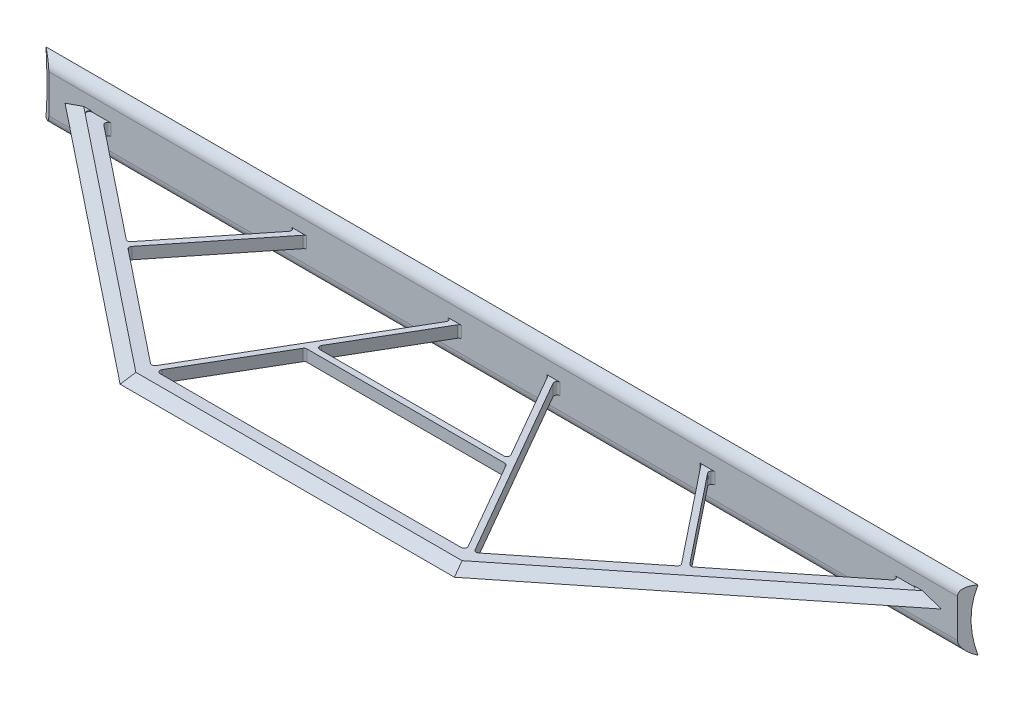
SolidWorks part; units mm, degrees
material "6061-T6 (SS)"
ref_plane "Front Plane" through (0, 0, 0) normal (0, 0, 1) x (1, 0, 0)
ref_plane "Top Plane" through (0, 0, 0) normal (0, 1, 0) x (1, 0, 0)
ref_plane "Right Plane" through (0, 0, 0) normal (1, 0, 0) x (0, 0, -1)
sketch "CS path" plane through (0, 0, 0) normal (0, 1, 0) x (1, 0, 0)
  line L0 (0, 0) -> (-228.6, 0) construction
  line L1 (0, 0) -> (228.6, 0) construction
  line L2 (0, 0) -> (0, -111.2988) construction
  line L3 (0, -111.2988) -> (88.9, -111.2988) construction
  line L4 (0, -111.2988) -> (-88.9, -111.2988) construction
  line L5 (88.9, -111.2988) -> (228.6, 0) construction
  line L6 (-88.9, -111.2988) -> (88.9, -111.2988)
  line L8 (228.6, 0) -> (248.466, 15.8272) construction
  line L9 (-88.9, -111.2988) -> (-228.6, 0) construction
  line L10 (-228.6, 0) -> (-248.466, 15.8272) construction
  line L11 (88.9, -111.2988) -> (248.466, 15.8272)
  line L12 (-88.9, -111.2988) -> (-248.466, 15.8272)
ref_plane "Plane4" through (248.466, 0, -15.8272) normal (0.7821, 0, -0.6231) x (-0.6231, 0, -0.7821)
sketch "Sketch7" plane through (248.466, 0, -15.8272) normal (0.7821, 0, -0.6231) x (-0.6231, 0, -0.7821)
  line L0 (0, 0) -> (0, 3.175) construction
  line L1 (110.7906, 0) -> (0, 0) construction
  line L2 (0, 3.175) -> (6.35, 3.175) construction
  line L3 (0, 0) -> (-6.35, 0) construction
  line L4 (0, 3.175) -> (0, 3.556)
  line L5 (6.35, 3.175) -> (0, 3.175)
  line L6 (0, 3.556) -> (-6.35, 0)
  line L7 (6.35, 3.175) -> (6.35, -3.175)
  line L8 (6.35, -3.175) -> (0, -3.175)
  line L9 (0, -3.175) -> (0, -3.556)
  line L10 (0, -3.556) -> (-6.35, 0)
sweep "Sweep2" add profiles "Sketch7" path "CS path"
sketch "Sketch8" plane through (0, 0, 0) normal (1, 0, 0) x (0, 0, -1)
  line L0 (0, 0) -> (82.804, 0) construction
  line L1 (82.804, 0) -> (-43.02, 26.7447) construction
  line L2 (82.804, 0) -> (-44.9942, -27.1644) construction
  line L3 (4.8299, 16.5739) -> (0, 17.6005)
  line L4 (4.8299, -16.5739) -> (0, -17.6005)
  line L5 (0, 17.6005) -> (0, -17.6005)
  line L6 (3.175, 0) -> (86.995, 0) construction
  arc A0 (4.8299, 16.5739) -> (4.8299, -16.5739) centre (86.995, 0) ccw
  dimension "D1" = 12
  dimension "D2" = 12
extrude "Boss-Extrude3" add sketch "Sketch8" along normal blind 254 and the other way blind 254 separate body
sketch "Sketch11" plane through (0, 0, 0) normal (0, 1, 0) x (1, 0, 0)
  line L3 (-86.6797, -104.9488) -> (-25.4, 0) construction
  line L4 (25.4, 0) -> (86.6797, -104.9488) construction
  line L6 (-25.4, 0) -> (-15.0913, 17.6549) construction
  line L7 (-86.6797, -104.9488) -> (-89.1388, -109.1603) construction
  line L8 (-89.1388, -109.1603) -> (-15.0913, 17.6549)
ref_plane "Plane5" through (-15.0913, 0, -17.6549) normal (0.5042, 0, -0.8636) x (-0.8636, 0, -0.5042)
sketch "Sketch12" plane through (-15.0913, 0, -17.6549) normal (0.5042, 0, -0.8636) x (-0.8636, 0, -0.5042)
  line L0 (0, 0) -> (0, -3.175) construction
  line L1 (0, -3.175) -> (1.5875, -3.175) construction
  line L2 (1.5875, -3.175) -> (1.5875, 3.175) construction
  line L3 (0, -3.175) -> (1.5875, -3.175)
  line L4 (1.5875, -3.175) -> (1.5875, 3.175)
  line L5 (1.5875, 3.175) -> (-1.5875, 3.175)
  line L6 (-1.5875, 3.175) -> (-1.5875, -3.175)
  line L7 (-1.5875, -3.175) -> (0, -3.175)
sweep "Sweep3" add profiles "Sketch12" path "Sketch11"
sketch "Sketch13" plane through (0, 0, 0) normal (0, 1, 0) x (1, 0, 0)
  line L2 (25.3355, 1.8095) -> (86.6797, -104.9488) construction
  line L3 (86.6797, -104.9488) -> (89.8434, -110.4546) construction
  line L4 (89.8434, -110.4546) -> (12.6343, 23.9135)
  line L5 (25.3355, 1.8095) -> (12.6343, 23.9135) construction
ref_plane "Plane6" through (12.6343, 0, -23.9135) normal (-0.4982, 0, -0.8671) x (-0.8671, 0, 0.4982)
sketch "Sketch14" plane through (12.6343, 0, -23.9135) normal (-0.4982, 0, -0.8671) x (-0.8671, 0, 0.4982)
  line L0 (0, 0) -> (0, -3.175) construction
  line L1 (0, -3.175) -> (1.5875, -3.175) construction
  line L2 (1.5875, -3.175) -> (1.5875, 3.175) construction
  line L3 (1.5875, 3.175) -> (-1.5875, 3.175) construction
  line L4 (0, -3.175) -> (1.5875, -3.175)
  line L5 (1.5875, -3.175) -> (1.5875, 3.175)
  line L6 (1.5875, 3.175) -> (-1.5875, 3.175)
  line L7 (-1.5875, 3.175) -> (-1.5875, -3.175)
  line L8 (-1.5875, -3.175) -> (0, -3.175)
sweep "Sweep5" add profiles "Sketch14" path "Sketch13"
sketch "Sketch15" plane through (254, 0, 0) normal (1, 0, 0) x (0, 0, -1)
  line L0 (4.8299, -16.5739) -> (30.9499, -16.5739)
  line L1 (30.9499, 16.5739) -> (30.9499, -16.5739)
  line L2 (4.8299, 16.5739) -> (30.9499, 16.5739)
  arc A0 (4.8299, 16.5739) -> (4.8299, -16.5739) centre (86.995, 0) ccw construction
  arc A2 (4.8299, 16.5739) -> (4.8299, -16.5739) centre (86.995, 0) ccw
extrude "Cut-Extrude1" cut sketch "Sketch15" against normal blind 508
ref_plane "Plane7" through (0, 17.6005, 0) normal (0, -1, 0) x (1, 0, 0)
sketch "Sketch17" plane through (0, 17.6005, 0) normal (0, -1, 0) x (1, 0, 0)
  line L0 (254, 0) -> (247.65, 0)
  line L1 (254, -4.8299) -> (254, 0) construction
  line L2 (-254, 0) -> (254, 0) construction
  line L3 (254, -4.8299) -> (254, 0)
  line L4 (247.65, 0) -> (254, -4.8299)
extrude "Cut-Extrude2" cut sketch "Sketch17" along normal blind 68.58
sketch "Sketch18" plane through (0, 17.6005, 0) normal (0, -1, 0) x (1, 0, 0)
  line L0 (-254, -4.8299) -> (-254, 0) construction
  line L1 (-254, 0) -> (-247.65, 0)
  line L2 (-254, 0) -> (247.65, 0) construction
  line L3 (-247.65, 0) -> (-254, -4.8299)
  line L4 (-254, -4.8299) -> (-254, 0)
extrude "Cut-Extrude3" cut sketch "Sketch18" along normal blind 68.834
sketch "Sketch19" plane through (0, 3.175, 0) normal (0, 1, 0) x (1, 0, 0)
  line L0 (218.4093, 0) -> (228.6, 0) construction
  line L1 (88.9, -111.2988) -> (228.6, 0) construction
  line L2 (223.8781, 0) -> (228.6, 0)
  line L3 (224.9069, -2.9423) -> (228.6, 0)
  arc A0 (224.9069, -2.9423) -> (223.8781, 0) centre (223.8781, -1.651) ccw
  dimension "D1" = 3.302
extrude "Boss-Extrude4" add sketch "Sketch19" against normal blind 6.731 and the other way blind 0.381
sketch "Sketch20" plane through (0, -3.175, 0) normal (0, -1, 0) x (1, 0, 0)
  line L0 (-88.9, 111.2988) -> (-248.466, -15.8272) construction
  line L1 (-228.6, 0) -> (-218.4093, 0) construction
  line L2 (-224.9069, 2.9423) -> (-228.6, 0)
  line L3 (-228.6, 0) -> (-223.8781, 0)
  arc A0 (-224.9069, 2.9423) -> (-223.8781, 0) centre (-223.8781, 1.651) ccw
  dimension "D1" = 3.302
extrude "Boss-Extrude5" add sketch "Sketch20" along normal blind 0.381 and the other way blind 6.731
sketch "Sketch21" plane through (0, 3.175, 0) normal (0, 1, 0) x (1, 0, 0)
  line L0 (-87.9344, -103.9493) -> (-27.2383, 0) construction
  line L1 (-84.8414, -104.9488) -> (-23.5617, 0) construction
  line L2 (84.8488, -104.9488) -> (-84.8414, -104.9488) construction
  line L3 (-87.9344, -103.9493) -> (-218.4093, 0) construction
  line L4 (-87.9344, -103.9493) -> (-86.9722, -102.3015)
  line L5 (-84.8414, -104.9488) -> (-83.3913, -102.4653)
  line L6 (84.8488, -104.9488) -> (81.996, -104.9488)
  line L7 (-87.9344, -103.9493) -> (-89.4268, -102.7603)
  line L8 (-247.65, 0) -> (247.65, 0) construction
  line L9 (84.8488, -104.9488) -> (24.5443, 0) construction
  line L10 (87.9357, -103.9482) -> (28.2061, 0) construction
  line L11 (-218.4093, 0) -> (-213.6875, 0)
  line L12 (84.8488, -104.9488) -> (83.4275, -102.4753)
  line L13 (87.9357, -103.9482) -> (86.9783, -102.2821)
  line L14 (87.9357, -103.9482) -> (218.4093, 0) construction
  line L15 (87.9357, -103.9482) -> (89.4386, -102.7509)
  line L16 (-218.4093, 0) -> (31.0589, 0)
  line L17 (213.6875, 0) -> (218.4093, 0)
  line L18 (213.6875, 0) -> (218.4093, 0)
  line L19 (25.0203, -0.8284) -> (24.5443, 0)
  line L20 (29.6274, -2.4736) -> (28.2061, 0)
  line L21 (214.7162, -2.9423) -> (218.4093, 0)
  line L22 (-81.9656, -104.9488) -> (-84.8414, -104.9488)
  line L23 (23.5888, 0) -> (31.0589, 0)
  line L24 (-24.0396, -0.8185) -> (-23.5617, 0)
  line L25 (-28.6884, -2.4835) -> (-27.2383, 0)
  line L26 (-30.1142, 0) -> (-22.6139, 0)
  line L27 (-214.7162, -2.9423) -> (-218.4093, 0)
  arc A0 (-213.6875, 0) -> (-214.7162, -2.9423) centre (-213.6875, -1.651) ccw
  arc A1 (-89.4268, -102.7603) -> (-86.9722, -102.3015) centre (-88.398, -101.469) ccw
  arc A2 (-28.6884, -2.4835) -> (-30.1142, 0) centre (-30.1142, -1.651) ccw
  arc A3 (-22.6139, 0) -> (-24.0396, -0.8185) centre (-22.6139, -1.651) ccw
  arc A4 (25.0203, -0.8284) -> (23.5888, 0) centre (23.5888, -1.651) ccw
  arc A5 (81.996, -104.9488) -> (83.4275, -102.4753) centre (81.996, -103.2978) ccw
  arc A6 (-83.3913, -102.4653) -> (-81.9656, -104.9488) centre (-81.9656, -103.2978) ccw
  arc A7 (31.0589, 0) -> (29.6274, -2.4736) centre (31.0589, -1.651) ccw
  arc A8 (214.7162, -2.9423) -> (213.6875, 0) centre (213.6875, -1.651) ccw
  arc A9 (86.9783, -102.2821) -> (89.4386, -102.7509) centre (88.4098, -101.4596) ccw
  line M17 (218.4093, 0) -> (87.9357, -103.9482)
  line M18 (87.9357, -103.9482) -> (28.2061, 0)
  line M20 (24.5443, 0) -> (84.8488, -104.9488)
  line M21 (84.8488, -104.9488) -> (-84.8414, -104.9488)
  line M22 (-84.8414, -104.9488) -> (-23.5617, 0)
  line M24 (-27.2383, 0) -> (-87.9344, -103.9493)
  line M25 (-87.9344, -103.9493) -> (-218.4093, 0)
  dimension "D1" = 3.302
  dimension "D2" = 3.302
  dimension "D3" = 3.302
  dimension "D4" = 3.302
  dimension "D5" = 3.302
  dimension "D6" = 3.302
  dimension "D7" = 3.302
  dimension "D8" = 3.302
  dimension "D9" = 3.302
  dimension "D10" = 3.302
extrude "Boss-Extrude6" add sketch "Sketch21" against normal blind 6.35 contours A1 M25 M24 | A6 M22 M21 | A0 L11 M25 | A2 L16 M24 | A3 L16 M22 | A7 L16 M18 | A4 L16 M20 | A5 M21 M20 | A8 L17 M17 | A9 L15 L13 region at (-88.0555, 3.175, 103.3013) region at (216.155, 3.175, 0.7882) region at (29.2535, 3.175, 0.6061) region at (-23.4631, 3.175, 0.1717) region at (-28.2999, 3.175, 0.6095) region at (-216.155, 3.175, 0.7882) region at (24.4437, 3.175, 0.1739) region at (-83.7798, 3.175, 104.3394) region at (83.8014, 3.175, 104.3427)
sketch "Sketch22" plane through (0, 3.175, 0) normal (0, 1, 0) x (1, 0, 0)
  line L1 (-152.0715, -52.8513) -> (-214.7162, -2.9423) construction
  line L2 (-152.0715, -52.8513) -> (-108.201, 2.2141) construction
  line L3 (-152.0715, -52.8513) -> (-108.201, 2.2141)
ref_plane "Plane8" through (-152.0715, 3.175, 52.8513) normal (0.6231, 0, -0.7821) x (-0.7821, 0, -0.6231)
sketch "Sketch23" plane through (-152.0715, 3.175, 52.8513) normal (0.6231, 0, -0.7821) x (-0.7821, 0, -0.6231)
  line L0 (0, 0) -> (0, -6.35) construction
  line L2 (0, 0) -> (80.0954, 0) construction
  line L3 (0, -6.35) -> (1.5875, -6.35) construction
  line L4 (1.5875, -6.35) -> (1.5875, 0) construction
  line L5 (0, -6.35) -> (1.5875, -6.35)
  line L6 (1.5875, -6.35) -> (1.5875, 0)
  line L7 (1.5875, 0) -> (-1.5875, 0)
  line L8 (-1.5875, 0) -> (-1.5875, -6.35)
  line L9 (-1.5875, -6.35) -> (0, -6.35)
sweep "Sweep6" add profiles "Sketch23" path "Sketch22"
sketch "Sketch24" plane through (0, 3.175, 0) normal (0, 1, 0) x (1, 0, 0)
  line L23 (89.4386, -102.7509) -> (152.0774, -52.8466) construction
  line L24 (152.0774, -52.8466) -> (109.9746, 0) construction
  line L25 (-247.65, 0) -> (247.65, 0) construction
  line L26 (-247.65, 0) -> (247.65, 0) construction
  line L27 (152.0774, -52.8466) -> (109.9746, 0)
ref_plane "Plane9" through (152.0774, 3.175, 52.8466) normal (-0.6231, 0, -0.7821) x (-0.7821, 0, 0.6231)
sketch "Sketch25" plane through (152.0774, 3.175, 52.8466) normal (-0.6231, 0, -0.7821) x (-0.7821, 0, 0.6231)
  line L0 (0, 0) -> (0, -6.35) construction
  line L1 (1.5875, 0) -> (0, 0)
  line L2 (0, -6.35) -> (1.5875, -6.35) construction
  line L3 (0, -6.35) -> (1.5875, -6.35)
  line L4 (1.5875, -6.35) -> (1.5875, 0)
  line L5 (0, -6.35) -> (-1.5875, -6.35) construction
  line L7 (0, -6.35) -> (-1.5875, -6.35)
  line L8 (-1.5875, -6.35) -> (-1.5875, 0)
  line L9 (279.7077, 0) -> (-107.6796, 0) construction
  line L10 (-1.5875, 0) -> (0, 0)
sweep "Sweep7" add profiles "Sketch25" path "Sketch24"
sketch "Sketch26" plane through (0, 3.175, 0) normal (0, 1, 0) x (1, 0, 0)
  line L0 (-53.7155, -51.6419) -> (54.2239, -51.6519)
  line L2 (-83.3913, -102.4653) -> (-53.7155, -51.6419) construction
  line L3 (54.2239, -51.6519) -> (25.0203, -0.8284) construction
ref_plane "Plane10" through (54.2239, 3.175, 51.6519) normal (1, 0, 0.0001) x (0.0001, 0, -1)
sketch "Sketch27" plane through (54.2239, 3.175, 51.6519) normal (1, 0, 0.0001) x (0.0001, 0, -1)
  line L0 (0, 0) -> (0, -6.35) construction
  line L1 (0, -6.35) -> (1.5875, -6.35) construction
  line L2 (0, -6.35) -> (-1.5875, -6.35) construction
  line L3 (0, -6.35) -> (1.5875, -6.35)
  line L4 (1.5875, -6.35) -> (1.5875, 0)
  line L5 (0, 0) -> (50.8207, 0) construction
  line L6 (1.5875, 0) -> (-1.5875, 0)
  line L7 (-50.8262, 0) -> (0, 0) construction
  line L8 (-1.5875, 0) -> (-1.5875, -6.35)
  line L9 (-1.5875, -6.35) -> (0, -6.35)
extrude "Boss-Extrude7" add sketch "Sketch27" against normal blind 110.49 and the other way blind 1.2701
sketch "Sketch28" plane through (0, 3.175, 0) normal (0, 1, 0) x (1, 0, 0)
  line L0 (-153.3131, -51.8621) -> (-214.7162, -2.9423) construction
  line L1 (-111.9947, 0) -> (-153.3131, -51.8621) construction
  line L2 (-247.65, 0) -> (247.65, 0) construction
  line L3 (-107.9352, 0) -> (-150.8299, -53.8405) construction
  line L4 (-89.4268, -102.7603) -> (-150.8299, -53.8405) construction
  line L5 (-153.3131, -51.8621) -> (-214.7162, -2.9423)
  line L6 (-111.9947, 0) -> (-114.1296, -2.6798)
  line L7 (-115.4209, 0) -> (-107.1396, 0)
  line L8 (-107.9352, 0) -> (-108.4309, -0.6222)
  line L9 (-149.5386, -54.8693) -> (-150.8299, -53.8405)
  line L10 (-83.3913, -102.4653) -> (-54.6424, -53.2293) construction
  line L11 (-52.7886, -50.0545) -> (-24.0396, -0.8185) construction
  line L12 (53.3117, -50.0643) -> (-52.7886, -50.0545) construction
  line L13 (55.1361, -53.2395) -> (-54.6424, -53.2293) construction
  line L14 (-55.1203, -54.0479) -> (-54.6424, -53.2293)
  line L15 (-52.7886, -50.0545) -> (-51.3386, -47.5713)
  line L16 (53.3117, -50.0643) -> (50.4585, -50.064)
  line L17 (55.1361, -53.2395) -> (54.1808, -53.2394)
  line L18 (153.319, -51.8574) -> (214.7162, -2.9423) construction
  line L19 (112.0043, 0) -> (153.319, -51.8574) construction
  line L20 (108.733, -0.9892) -> (150.8358, -53.8358) construction
  line L21 (89.4386, -102.7509) -> (150.8358, -53.8358) construction
  line L22 (153.319, -51.8574) -> (154.6103, -50.8286)
  line L23 (112.0043, 0) -> (114.1393, -2.6798)
  line L24 (149.807, -52.5445) -> (150.8358, -53.8358)
  line L25 (149.5445, -54.8645) -> (150.8358, -53.8358)
  line L26 (53.3117, -50.0643) -> (25.0203, -0.8284) construction
  line L27 (53.3117, -50.0643) -> (51.8902, -47.5905)
  line L28 (83.4275, -102.4753) -> (55.1361, -53.2395) construction
  line L29 (55.6121, -54.0678) -> (55.1361, -53.2395)
  line L30 (108.733, -0.9892) -> (150.8358, -53.8358)
  line L31 (108.733, -0.9892) -> (107.9449, 0)
  line L32 (107.1493, 0) -> (109.9746, 0)
  line L33 (112.0043, 0) -> (115.4306, 0)
  line L34 (152.2903, -50.5661) -> (153.319, -51.8574)
  line L35 (-53.6944, -53.2294) -> (-54.6424, -53.2293)
  line L36 (-49.913, -50.0548) -> (-52.7886, -50.0545)
  line L37 (-149.8011, -52.5492) -> (-150.8299, -53.8405)
  line L38 (-152.2844, -50.5708) -> (-153.3131, -51.8621)
  arc A0 (-154.6044, -50.8333) -> (-152.2844, -50.5708) centre (-153.5756, -49.542) ccw
  arc A1 (-114.1296, -2.6798) -> (-115.4209, 0) centre (-115.4209, -1.651) ccw
  arc A2 (-149.8011, -52.5492) -> (-149.5386, -54.8693) centre (-148.5098, -53.578) ccw
  arc A3 (-107.1396, 0) -> (-108.4309, -0.6222) centre (-107.1396, -1.651) ccw
  arc A4 (-53.6944, -53.2294) -> (-55.1203, -54.0479) centre (-53.6946, -54.8804) ccw
  arc A5 (-51.3386, -47.5713) -> (-49.913, -50.0548) centre (-49.9129, -48.4038) ccw
  arc A6 (50.4585, -50.064) -> (51.8902, -47.5905) centre (50.4587, -48.413) ccw
  arc A7 (55.6121, -54.0678) -> (54.1808, -53.2394) centre (54.1806, -54.8904) ccw
  arc A8 (108.4406, -0.6222) -> (107.1493, 0) centre (107.1493, -1.651) ccw
  arc A9 (149.5445, -54.8645) -> (149.807, -52.5445) centre (148.5157, -53.5733) ccw
  arc A10 (115.4306, 0) -> (114.1393, -2.6798) centre (115.4306, -1.651) ccw
  arc A11 (152.2903, -50.5661) -> (154.6103, -50.8286) centre (153.5816, -49.5373) ccw
  line M1 (25.0203, -0.8284) -> (53.3117, -50.0643)
  line M2 (53.3117, -50.0643) -> (-52.7886, -50.0545)
  line M3 (-52.7886, -50.0545) -> (-24.0396, -0.8185)
  line M9 (-89.4268, -102.7603) -> (-150.8299, -53.8405)
  line M10 (-150.8299, -53.8405) -> (-107.9352, 0)
  line M12 (-111.9947, 0) -> (-153.3131, -51.8621)
  line M13 (-153.3131, -51.8621) -> (-214.7162, -2.9423)
  line M25 (214.7162, -2.9423) -> (153.319, -51.8574)
  line M26 (153.319, -51.8574) -> (112.0043, 0)
  line M29 (109.9746, 0) -> (108.733, -0.9892)
  line M30 (108.733, -0.9892) -> (150.8358, -53.8358)
  line M31 (150.8358, -53.8358) -> (89.4386, -102.7509)
  line M37 (-83.3913, -102.4653) -> (-54.6424, -53.2293)
  line M38 (-54.6424, -53.2293) -> (55.1361, -53.2395)
  line M39 (55.1361, -53.2395) -> (83.4275, -102.4753)
  dimension "D1" = 3.302
  dimension "D3" = 3.302
  dimension "D4" = 3.302
  dimension "D5" = 3.302
  dimension "D6" = 3.302
  dimension "D7" = 3.302
  dimension "D8" = 3.302
  dimension "D9" = 3.302
  dimension "D10" = 3.302
  dimension "D11" = 3.302
  dimension "D12" = 3.302
extrude "Boss-Extrude9" add sketch "Sketch28" against normal blind 6.35 contours A8 L31 L32 | L32 L31 M29 | A10 L33 M26 | A11 M26 M25 | A9 M31 M30 | A6 M2 M1 | A7 M39 M38 | A5 M3 M2 | A4 M38 M37 | A1 L7 M12 | A3 L7 M10 | A2 M10 M9 | A0 M13 M12 region at (-150.3116, 3.175, 53.7819) region at (-107.8731, 3.175, 0.1289) region at (-113.4036, 3.175, 0.6789) region at (-153.3718, 3.175, 51.3439) region at (55.0355, 3.175, 53.4133) region at (-54.5438, 3.175, 53.401) region at (52.2642, 3.175, 49.458) region at (-51.7271, 3.175, 49.4452) region at (153.3777, 3.175, 51.3391) region at (113.4133, 3.175, 0.6789) region at (108.8842, 3.175, 0.3297) region at (150.3176, 3.175, 53.7771) region at (107.8828, 3.175, 0.1289)
fillet "Fillet1" radius 6.35 2 edges at (0, -17.6005, 0) (0, 17.6005, 0)
